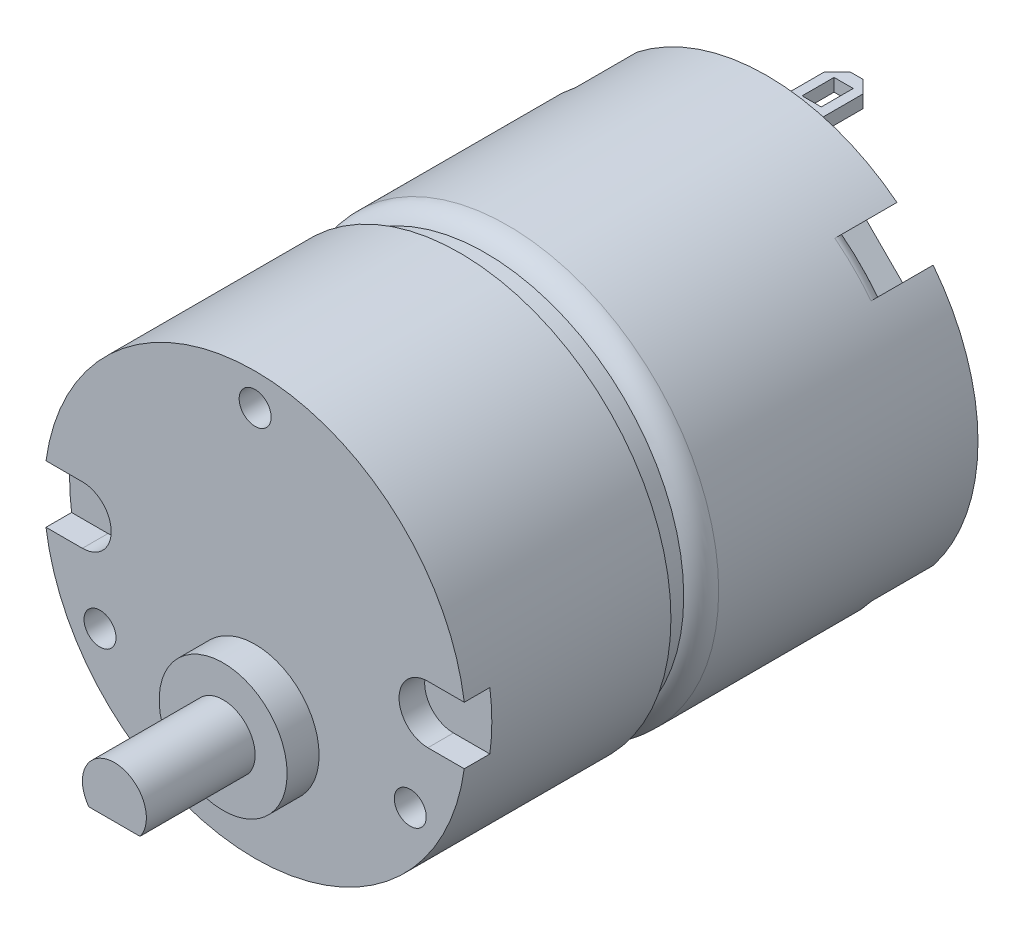
SolidWorks part; units mm, degrees
ref_plane "Front Plane" through (0, 0, 0) normal (0, 0, 1) x (1, 0, 0)
ref_plane "Top Plane" through (0, 0, 0) normal (0, 1, 0) x (1, 0, 0)
ref_plane "Right Plane" through (0, 0, 0) normal (1, 0, 0) x (0, 0, -1)
sketch "Sketch1" plane through (0, 0, 0) normal (0, 0, 1) x (1, 0, 0)
  circle A0 centre (0, 0) radius 16.5
  dimension "D1" = 33
extrude "Boss-Extrude1" add sketch "Sketch1" along normal blind 40
sketch "Sketch2" plane through (0, 0, 40) normal (0, 0, 1) x (1, 0, 0)
  circle A0 centre (0, 14) radius 1.25
  circle A2 centre (12.1244, -7) radius 1.25
  circle A3 centre (-12.1244, -7) radius 1.25
  point P9 (0, 0)
  dimension "D1" = 2.5
  dimension "D2" = 14
  dimension "D3" = 3
extrude "Cut-Extrude1" cut sketch "Sketch2" against normal blind 5
sketch "Sketch3" plane through (0, 0, 40) normal (0, 0, 1) x (1, 0, 0)
  circle A0 centre (0, -7) radius 5
  dimension "D1" = 10
extrude "Boss-Extrude2" add sketch "Sketch3" along normal blind 2.5
sketch "Sketch4" plane through (0, 0, 42.5) normal (0, 0, 1) x (1, 0, 0)
  line L0 (-2, -8.5) -> (2, -8.5)
  line L1 (0, -4.5) -> (1.7566, -4.5) construction
  arc A0 (2, -8.5) -> (-2, -8.5) centre (0, -7) ccw
  dimension "D1" = 5
  dimension "D2" = 4
extrude "Boss-Extrude3" add sketch "Sketch4" along normal blind 8.5
sketch "Sketch5" plane through (0, 0, 40) normal (0, 0, 1) x (1, 0, 0)
  line L0 (-16.5, 0) -> (-16.5, -3.2222) construction
  line L1 (-13.5, 2.25) -> (-17.6226, 2.25)
  line L2 (-17.6226, 2.25) -> (-17.6226, -2.25)
  line L3 (-17.6226, -2.25) -> (-13.5, -2.25)
  line L4 (0, 49.5) -> (0, -16.5) construction
  line L5 (17.6226, -2.25) -> (13.5, -2.25)
  line L6 (17.6226, 2.25) -> (17.6226, -2.25)
  line L7 (13.5, 2.25) -> (17.6226, 2.25)
  arc A0 (-13.5, -2.25) -> (-13.5, 2.25) centre (-13.5, 0) ccw
  circle A1 centre (0, 0) radius 16.5 construction
  arc A2 (13.5, -2.25) -> (13.5, 2.25) centre (13.5, 0) cw
  point P13 (0, 16.5)
  dimension "D1" = 4.5
  dimension "D2" = 3
extrude "Cut-Extrude2" cut sketch "Sketch5" against normal blind 2
sketch "Sketch6" plane through (0, 0, 40) normal (0, 0, 1) x (1, 0, 0)
  circle A0 centre (0, 0) radius 17.1941
  circle A1 centre (0, 0) radius 15.5
  dimension "D1" = 31
extrude "Cut-Extrude3" cut sketch "Sketch6" against normal blind 2 from offset 16 offset against normal yes
fillet "Fillet1" radius 2 1 edges at (16.5, 0, 22)
sketch "Sketch7" plane through (0, 0, 0) normal (0, 0, -1) x (-1, 0, 0)
  circle A0 centre (0, 0) radius 4.1
  dimension "D1" = 8.2
extrude "Boss-Extrude4" add sketch "Sketch7" along normal blind 3
sketch "Sketch8" plane through (0, 0, 0) normal (0, 0, -1) x (-1, 0, 0)
  line L0 (-49.5, 0) -> (16.5, 0) construction
  line L1 (0, 49.5) -> (0, -16.5) construction
  circle A0 centre (0, 12.5) radius 2.5
  circle A1 centre (0, 0) radius 16.5 construction
  circle A2 centre (0, -12.5) radius 2.5
  point P8 (-16.5, 0)
  point P11 (0, 16.5)
  dimension "D1" = 5
  dimension "D2" = 12.5
extrude "Boss-Extrude5" add sketch "Sketch8" along normal blind 1
sketch "Sketch9" plane through (0, 0, -1) normal (0, 0, -1) x (-1, 0, 0)
  line L0 (-49.5, 0) -> (16.5, 0) construction
  line L1 (-1.5, -13) -> (1.5, -13)
  line L2 (-1.5, -13) -> (-1.5, -12)
  line L3 (-1.5, -12) -> (1.5, -12)
  line L4 (1.5, -13) -> (1.5, -12)
  line L5 (-1.5, -13) -> (1.5, -12) construction
  line L6 (-1.5, -12) -> (1.5, -13) construction
  line L7 (-1.5, 12) -> (1.5, 12)
  line L8 (1.5, 13) -> (1.5, 12)
  line L9 (-1.5, 13) -> (1.5, 13)
  line L10 (-1.5, 13) -> (-1.5, 12)
  circle A0 centre (0, 0) radius 16.5 construction
  point P0 (0, -12.5)
  point P12 (-16.5, 0)
  dimension "D1" = 3
  dimension "D2" = 1
extrude "Boss-Extrude6" add sketch "Sketch9" along normal blind 6
sketch "Sketch10" plane through (0, 13, 0) normal (0, 1, 0) x (1, 0, 0)
  line L0 (-1.5, 7) -> (-0.5, 7)
  line L1 (-1.5, 7) -> (1.5, 7) construction
  line L2 (1.5, 7) -> (0.5, 7)
  line L3 (-1.5, 7) -> (-1.5, 6)
  line L4 (-1.5, 7) -> (-1.5, 1) construction
  line L5 (-1.5, 6) -> (-0.5, 7)
  line L6 (1.5, 7) -> (1.5, 6)
  line L7 (1.5, 7) -> (1.5, 1) construction
  line L8 (1.5, 6) -> (0.5, 7)
  dimension "D2" = 1
  dimension "D1" = 1
  dimension "D3" = 1
  dimension "D4" = 1
extrude "Cut-Extrude4" cut sketch "Sketch10" against normal through all
sketch "Sketch11" plane through (0, 13, 0) normal (0, 1, 0) x (1, 0, 0)
  line L0 (1.5, 6) -> (1.5, 1) construction
  line L1 (-0.75, 6) -> (0.75, 6)
  line L2 (-0.75, 6) -> (-0.75, 3.5)
  line L3 (-0.75, 3.5) -> (0.75, 3.5)
  line L4 (0.75, 6) -> (0.75, 3.5)
  dimension "D1" = 1.5
  dimension "D2" = 2.5
  dimension "D3" = 0.75
extrude "Cut-Extrude5" cut sketch "Sketch11" against normal through all
sketch "Sketch12" plane through (0, 0, 0) normal (0, 0, -1) x (-1, 0, 0)
  line L0 (0, 0) -> (16.5, 0) construction
  line L1 (0, 0) -> (11.6673, 11.6673) construction
  line L2 (7.7782, 10.6066) -> (11.6927, 14.5212)
  line L3 (10.6066, 7.7782) -> (14.5278, 11.6994)
  line L4 (7.7782, 10.6066) -> (10.6066, 7.7782)
  line L5 (11.6927, 14.5212) -> (14.5278, 11.6994)
  line L6 (10.6066, -7.7782) -> (14.5212, -11.6927)
  line L7 (14.5212, -11.6927) -> (11.6994, -14.5278)
  line L8 (7.7782, -10.6066) -> (11.6994, -14.5278)
  line L9 (10.6066, -7.7782) -> (7.7782, -10.6066)
  line L10 (-7.7782, -10.6066) -> (-11.6927, -14.5212)
  line L11 (-11.6927, -14.5212) -> (-14.5278, -11.6994)
  line L12 (-10.6066, -7.7782) -> (-14.5278, -11.6994)
  line L13 (-7.7782, -10.6066) -> (-10.6066, -7.7782)
  line L14 (-10.6066, 7.7782) -> (-14.5212, 11.6927)
  line L15 (-14.5212, 11.6927) -> (-11.6994, 14.5278)
  line L16 (-7.7782, 10.6066) -> (-11.6994, 14.5278)
  line L17 (-10.6066, 7.7782) -> (-7.7782, 10.6066)
  circle A0 centre (0, 0) radius 16.5 construction
  point P26 (0, 0)
  dimension "D1" = 2
  dimension "D2" = 2
  dimension "D3" = 3.5
  dimension "D4" = 4
extrude "Cut-Extrude6" cut sketch "Sketch12" against normal blind 3.85
fillet "Fillet2" radius 1 4 edges at (-11.6673, 11.6673, 3.85) (-11.6673, -11.6673, 3.85) (11.6673, -11.6673, 3.85) (11.6673, 11.6673, 3.85)
